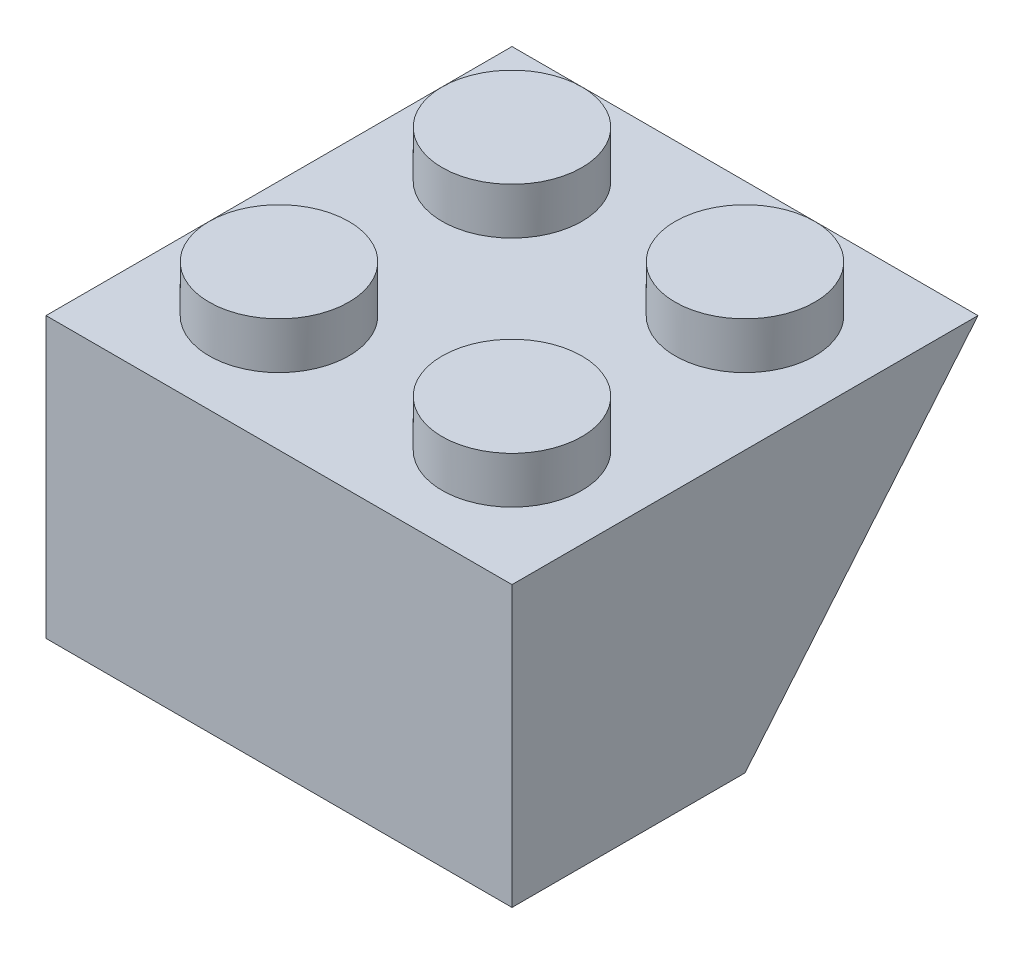
SolidWorks part; units mm, degrees
ref_plane "Front Plane" through (0, 0, 0) normal (0, 0, 1) x (1, 0, 0)
ref_plane "Top Plane" through (0, 0, 0) normal (0, 1, 0) x (1, 0, 0)
ref_plane "Right Plane" through (0, 0, 0) normal (1, 0, 0) x (0, 0, -1)
sketch "Sketch1" plane through (0, 0, 0) normal (0, 1, 0) x (1, 0, 0)
  line L1 (0, 0) -> (16, 0)
  line L2 (0, 0) -> (0, 8)
  line L3 (0, 8) -> (16, 8)
  line L4 (16, 0) -> (16, 8)
  dimension "D1" = 8
  dimension "D2" = 16
ref_plane "Plane1" through (0, 9.6, 0) normal (0, 1, 0) x (1, 0, 0)
sketch "Sketch2" plane through (0, 9.6, 0) normal (0, 1, 0) x (1, 0, 0)
  line L1 (0, 0) -> (16, 0)
  line L2 (0, 0) -> (0, 16)
  line L3 (0, 16) -> (16, 16)
  line L4 (16, 0) -> (16, 16)
  dimension "D1" = 16
  dimension "D2" = 16
loft "Loft1" add profiles "Sketch2", "Sketch1" connector at (0, 9.6, 0) connector at (0, 0, 0)
sketch "Sketch3" plane through (0, 9.6, 0) normal (0, 1, 0) x (1, 0, 0)
  line L0 (16, 0) -> (12, 0) construction
  line L1 (0, 0) -> (16, 0) construction
  line L2 (12, 0) -> (12, 4) construction
  circle A0 centre (12, 4) radius 2.4
  dimension "D3" = 4.8
  dimension "D1" = 4
  dimension "D2" = 4
extrude "Boss-Extrude1" add sketch "Sketch3" along normal blind 1.6
pattern_linear "LPattern1" count 2 spacing 8 along (0, 0, -1) count 2 spacing 8 along (-1, 0, 0) of "Boss-Extrude1"
shell "Shell1" thickness 1.6 removed face at (8, 0, -4)
